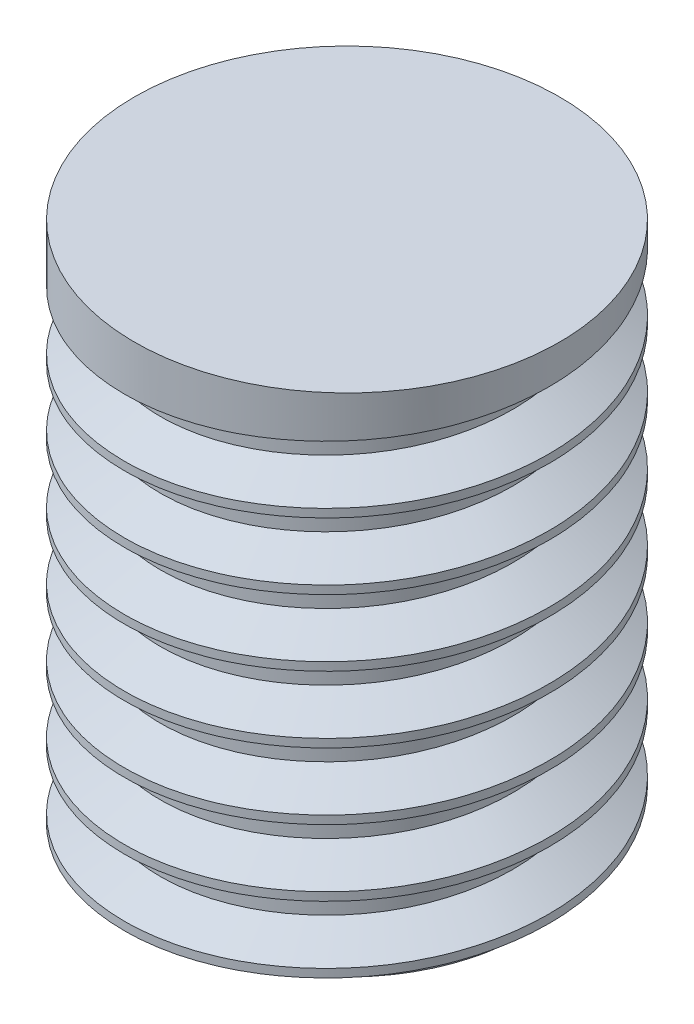
SolidWorks part; units mm, degrees
ref_plane "Front Plane" through (0, 0, 0) normal (0, 0, 1) x (1, 0, 0)
ref_plane "Top Plane" through (0, 0, 0) normal (0, 1, 0) x (1, 0, 0)
ref_plane "Right Plane" through (0, 0, 0) normal (1, 0, 0) x (0, 0, -1)
sketch "Sketch1" plane through (0, 0, 0) normal (0, 1, 0) x (1, 0, 0)
  circle A0 centre (0, 0) radius 4
extrude "Boss-Extrude1" add sketch "Sketch1" along normal blind 10
thread "Thread1" pitch 1.25 method cut profile "Thread Profile1" start angle 0, offset 0, length 10, pitch 1.25, diameter 8
ref_plane "Plane1" through (-4, 10, 0) normal (0, 0, 1) x (-1, 0, 0)
sketch "Thread Profile1" plane through (-4, 10, 0) normal (0, 0, 1) x (-1, 0, 0)
  line L0 (0, 0) -> (0, 1.25) construction
  line L11 (0, 0) -> (0, 1.0937)
  line L12 (0, 1.0937) -> (-0.6766, 0.7031)
  line L13 (-0.6766, 0.7031) -> (-0.6766, 0.3906)
  line L15 (-0.6766, 0.3906) -> (0, 0)
  line L17 (-0.6766, 0.5469) -> (0, 0.5469) construction
  point P2 (0, 0)
  dimension "Pitch" = 1.25
  dimension "Profile_Angle" = 60
  dimension "Profile_Land" = 0.3125
  dimension "Profile_Height" = 0.6766
